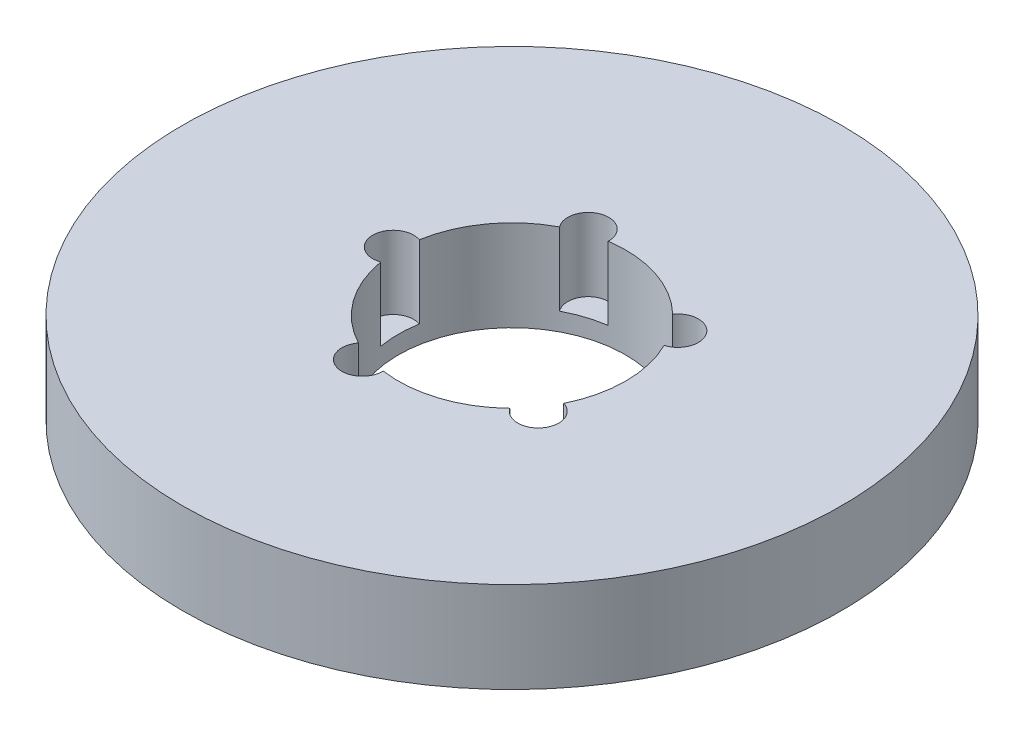
SolidWorks part; units mm, degrees
ref_plane "Front Plane" through (0, 0, 0) normal (0, 0, 1) x (1, 0, 0)
ref_plane "Top Plane" through (0, 0, 0) normal (0, 1, 0) x (1, 0, 0)
ref_plane "Right Plane" through (0, 0, 0) normal (1, 0, 0) x (0, 0, -1)
sketch "Sketch1" plane through (0, 0, 0) normal (0, 1, 0) x (1, 0, 0)
  circle A0 centre (0, 0) radius 72.5
  dimension "FLANGE_OD" = 145
extrude "Boss-Extrude1" add sketch "Sketch1" along normal blind 20
sketch "Sketch2" plane through (0, 0, 0) normal (0, 1, 0) x (1, 0, 0)
  circle A0 centre (0, 0) radius 25
  dimension "BORE_D" = 50
extrude "Cut-Extrude1" cut sketch "Sketch2" along normal through all
sketch "Sketch3" plane through (0, 20, 0) normal (0, 1, 0) x (1, 0, 0)
  circle A0 centre (0, 0) radius 26.1309 construction
  circle A1 centre (-26.1309, 0) radius 4.5027
  dimension "BOLT_D" = 9.0055
  dimension "BOLT_PCD" = 52.2618
extrude "Cut-Extrude2" cut sketch "Sketch3" against normal blind 16.0535
pattern_circular "CirPattern1" count 5 over 360 about axis through (0, 0, 0) along (0, 1, 0) of "Cut-Extrude2"
